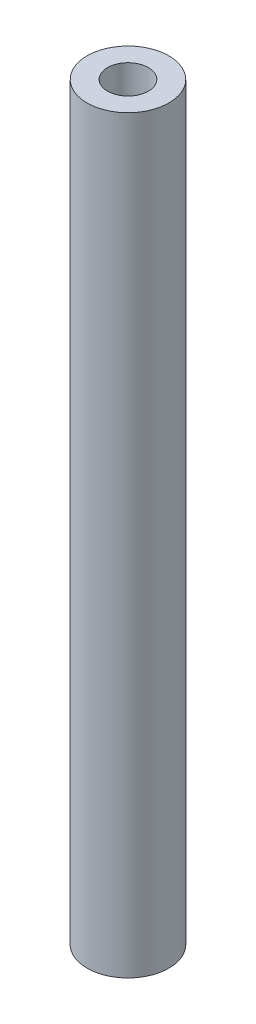
SolidWorks part; units mm, degrees
ref_plane "Front Plane" through (0, 0, 0) normal (0, 0, 1) x (1, 0, 0)
ref_plane "Top Plane" through (0, 0, 0) normal (0, 1, 0) x (1, 0, 0)
ref_plane "Right Plane" through (0, 0, 0) normal (1, 0, 0) x (0, 0, -1)
sketch "Sketch1" plane through (0, 0, 0) normal (0, 1, 0) x (1, 0, 0)
  circle A0 centre (0, 0) radius 1.5
  circle A1 centre (0, 0) radius 3
  dimension "D1" = 3
  dimension "D2" = 6
extrude "Boss-Extrude1" add sketch "Sketch1" along normal blind 55
